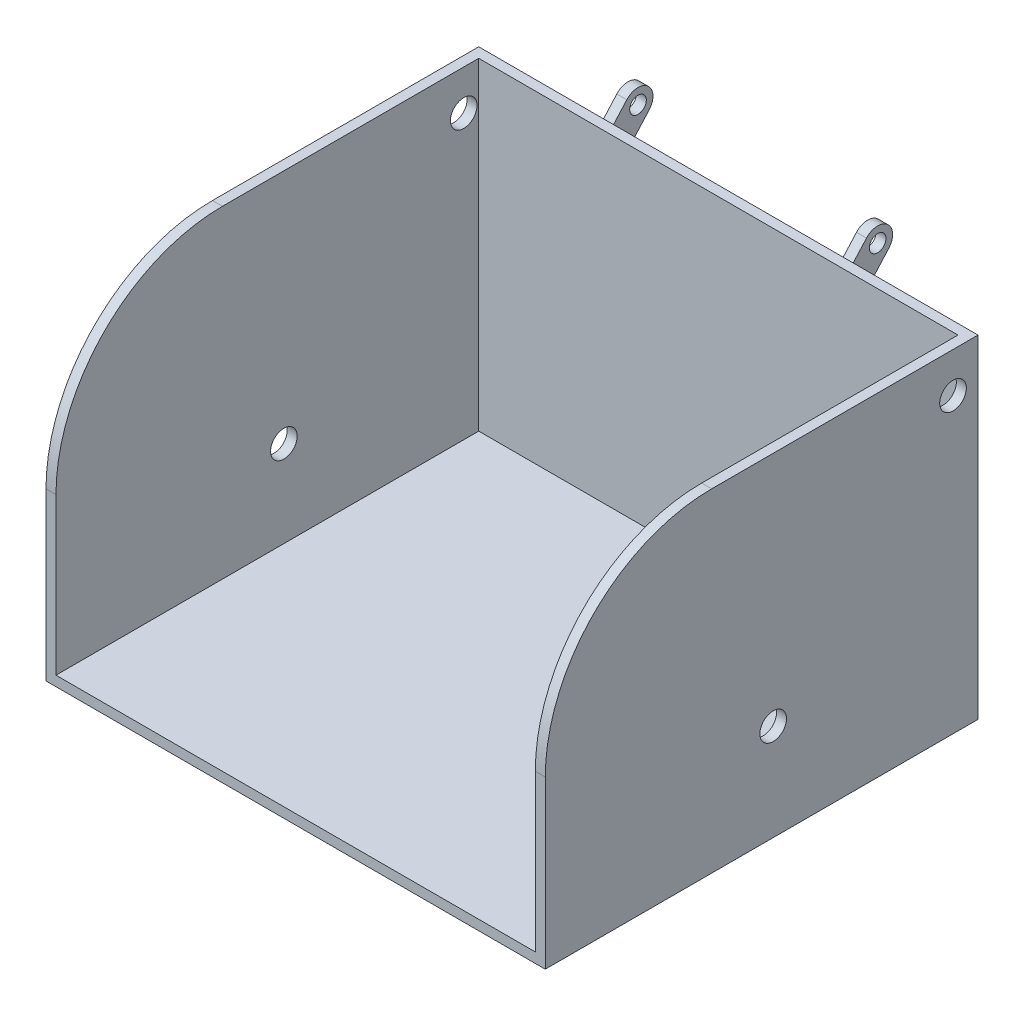
SolidWorks part; units mm, degrees
ref_plane "Front Plane" through (0, 0, 0) normal (0, 0, 1) x (1, 0, 0)
ref_plane "Top Plane" through (0, 0, 0) normal (0, 1, 0) x (1, 0, 0)
ref_plane "Right Plane" through (0, 0, 0) normal (1, 0, 0) x (0, 0, -1)
sketch "Sketch1" plane through (0, 0, 0) normal (1, 0, 0) x (0, 0, -1)
  line L0 (0, 0) -> (-130, 0)
  line L1 (-130, 0) -> (-130, 50)
  line L2 (-80, 100) -> (0, 100)
  line L3 (0, 100) -> (0, 0)
  arc A0 (-130, 50) -> (-80, 100) centre (-80, 50) cw
  point P6 (0, 71.5084)
  point P8 (-108.0821, 29.5905)
  point P9 (0, 0)
  point P10 (0, 0)
  point P11 (-110.8215, 32.3299)
  dimension "D1" = 130
  dimension "D2" = 100
  dimension "D3" = 50
extrude "Boss-Extrude1" add sketch "Sketch1" along normal blind 150 contours A0 L2 L3 L0 L1
sketch "Sketch2" plane through (0, 100, 0) normal (0, 1, 0) x (1, 0, 0)
  line L0 (150, 0) -> (0, 0) construction
  line L1 (3, -3) -> (147, -3)
  line L2 (3, -3) -> (3, -135)
  line L3 (3, -135) -> (147, -135)
  line L4 (147, -3) -> (147, -135)
  line L5 (150, -80) -> (150, 0) construction
  line L6 (0, -80) -> (0, 0) construction
  line L8 (150, -130) -> (0, -130) construction
  dimension "D1" = 3
  dimension "D2" = 3
  dimension "D3" = 3
  dimension "D4" = 5
extrude "Cut-Extrude1" cut sketch "Sketch2" against normal offset from surface (97 mm away) 3 up to face at (75, 0, 65)
ref_plane "Plane1" through (75, 0, 0) normal (1, 0, 0) x (0, 0, -1)
ref_plane "Plane2" through (111, 0, 0) normal (1, 0, 0) x (0, 0, -1)
ref_plane "Plane3" through (39, 0, 0) normal (1, 0, 0) x (0, 0, -1)
sketch "Sketch3" plane through (111, 0, 0) normal (1, 0, 0) x (0, 0, -1)
  line L0 (0, 100) -> (0, 86.4837)
  line L1 (0, 86.4837) -> (10.7098, 98.4837)
  line L2 (3.9952, 104.4764) -> (0, 100)
  arc A0 (10.7098, 98.4837) -> (3.9952, 104.4764) centre (7.3525, 101.4801) ccw
  circle A1 centre (7.3525, 101.4801) radius 2.5
  dimension "D1" = 2
  dimension "D2" = 5
  dimension "D3" = 6
  dimension "D4" = 12
extrude "Boss-Extrude2" add sketch "Sketch3" along normal mid plane 3
mirror "Mirror1" about plane through (75, 0, 0) normal (1, 0, 0) of "Boss-Extrude2"
sketch "Sketch4" plane through (150, 0, 0) normal (1, 0, 0) x (0, 0, -1)
  line L0 (-7.5037, 88) -> (-61.5315, 29) construction
  line L1 (0, 0) -> (-130, 0) construction
  line L2 (-80, 100) -> (0, 100) construction
  circle A0 centre (-61.5315, 29) radius 4
  circle A1 centre (-7.5037, 88) radius 4
  dimension "D4" = 8
  dimension "D5" = 8
  dimension "D1" = 80
  dimension "D2" = 29
  dimension "D3" = 12
extrude "Cut-Extrude2" cut sketch "Sketch4" against normal up to next contours A0 | A1 region at (150, 29, 61.5315) region at (150, 88, 7.5037)
mirror "Mirror2" about plane through (75, 0, 0) normal (1, 0, 0) of "Cut-Extrude2"
equation "\"forward_length\" = 130"
equation "\"height\"= 100"
equation "\"eslabon_AB\"=80"
